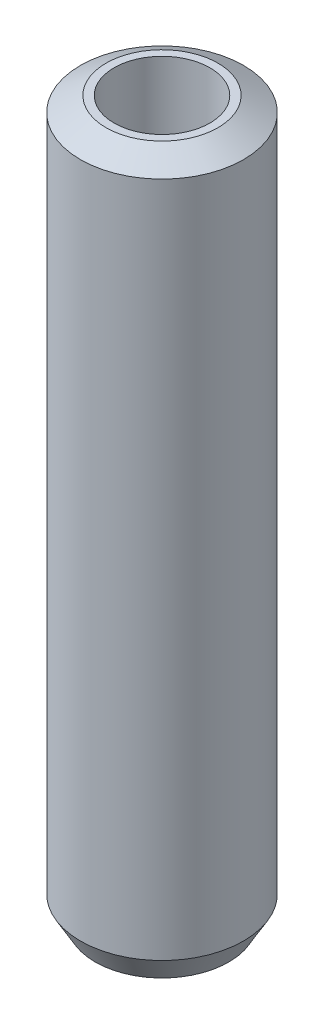
SolidWorks part; units mm, degrees
ref_plane "Front Plane" through (0, 0, 0) normal (0, 0, 1) x (1, 0, 0)
ref_plane "Top Plane" through (0, 0, 0) normal (0, 1, 0) x (1, 0, 0)
ref_plane "Right Plane" through (0, 0, 0) normal (1, 0, 0) x (0, 0, -1)
sketch "Sketch1" plane through (0, 0, 0) normal (0, 1, 0) x (1, 0, 0)
  circle A0 centre (0, 0) radius 7.5
  dimension "SHAFT_OD" = 15
extrude "Boss-Extrude1" add sketch "Sketch1" along normal blind 65.9212
sketch "Sketch2" plane through (0, 0, 0) normal (0, 1, 0) x (1, 0, 0)
  circle A0 centre (0, 0) radius 4.4058
  dimension "BORE_D" = 8.8117
extrude "Cut-Extrude1" cut sketch "Sketch2" along normal through all
chamfer "Chamfer1" distance 1.3599 angle 60 2 edges at (0, 65.9212, 7.5) (0, 0, 7.5) first distance on face at (0, 65.9212, 7.5) first distance on face at (0, 0, 4.4058)
